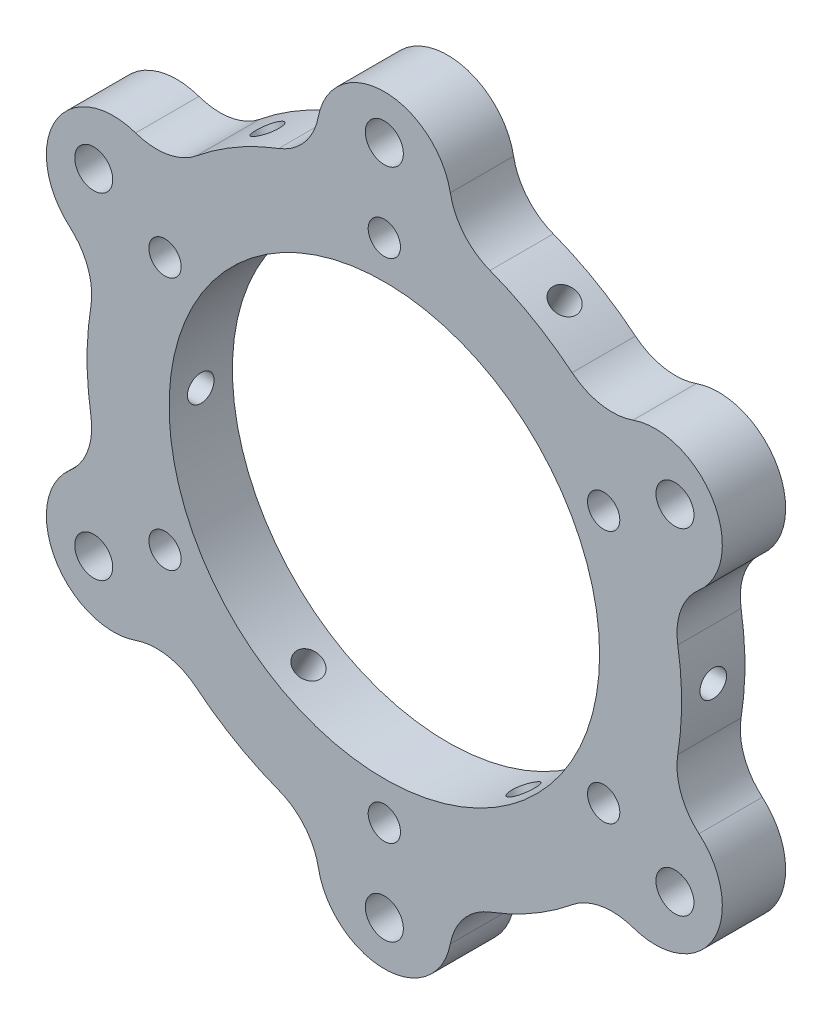
SolidWorks part; units mm, degrees
material "6063-T6"
ref_plane "Front Plane" through (0, 0, 0) normal (0, 0, 1) x (1, 0, 0)
ref_plane "Top Plane" through (0, 0, 0) normal (0, 1, 0) x (1, 0, 0)
ref_plane "Right Plane" through (0, 0, 0) normal (1, 0, 0) x (0, 0, -1)
sketch "Sketch5" plane through (0, 0, 0) normal (0, 1, 0) x (1, 0, 0)
  line L0 (0, -16.5008) -> (0, 15.0181) construction
ref_plane "Plane1" through (0, 0, 0) normal (-0.5, 0.866, 0) x (0, 0, -1)
sketch "Sketch2" plane through (0, 0, 0) normal (0, 0, 1) x (1, 0, 0)
  line L0 (0, 0) -> (0, 53) construction
  line L1 (0, 0) -> (0, 40) construction
  line L2 (0, 0) -> (0, 53) construction
  circle A0 centre (0, 0) radius 34
  circle A1 centre (0, 0) radius 60
  circle A2 centre (0, 53) radius 3
  circle A3 centre (45.8993, 26.5) radius 3
  circle A4 centre (45.8993, -26.5) radius 3
  circle A5 centre (0, -53) radius 3
  circle A6 centre (-45.8993, -26.5) radius 3
  circle A7 centre (-45.8993, 26.5) radius 3
  circle A11 centre (0, 0) radius 53 construction
  circle A12 centre (0, 40) radius 2.55
  circle A13 centre (34.641, 20) radius 2.55
  circle A14 centre (34.641, -20) radius 2.55
  circle A15 centre (0, -40) radius 2.55
  circle A16 centre (-34.641, -20) radius 2.55
  circle A17 centre (-34.641, 20) radius 2.55
  circle A18 centre (0, 0) radius 44.45 construction
  arc A19 (-16.6885, 43.8839) -> (16.6885, 43.8839) centre (0, 0) ccw
  arc A21 (-10.4177, 51.3701) -> (10.4177, 51.3701) centre (0, 49.3971) cw
  arc A22 (10.4177, 51.3701) -> (16.6885, 43.8839) centre (20.2431, 53.2308) ccw
  circle A23 centre (0, 0) radius 46.95 construction
  arc A24 (-10.4177, 51.3701) -> (-16.6885, 43.8839) centre (-20.2431, 53.2308) cw
  arc A25 (39.2789, 34.707) -> (49.6966, 16.663) centre (42.7791, 24.6985) cw
  arc A26 (39.2789, 34.707) -> (29.6603, 36.3946) centre (35.9777, 44.1464) cw
  arc A27 (49.6966, 16.663) -> (46.3488, 7.4892) centre (56.2208, 9.0844) ccw
  arc A28 (49.6966, -16.663) -> (39.2789, -34.707) centre (42.7791, -24.6985) cw
  arc A29 (49.6966, -16.663) -> (46.3488, -7.4892) centre (56.2208, -9.0844) cw
  arc A30 (39.2789, -34.707) -> (29.6603, -36.3946) centre (35.9777, -44.1464) ccw
  arc A31 (10.4177, -51.3701) -> (-10.4177, -51.3701) centre (0, -49.3971) cw
  arc A32 (10.4177, -51.3701) -> (16.6885, -43.8839) centre (20.2431, -53.2308) cw
  arc A33 (-10.4177, -51.3701) -> (-16.6885, -43.8839) centre (-20.2431, -53.2308) ccw
  arc A34 (-39.2789, -34.707) -> (-49.6966, -16.663) centre (-42.7791, -24.6985) cw
  arc A35 (-39.2789, -34.707) -> (-29.6603, -36.3946) centre (-35.9777, -44.1464) cw
  arc A36 (-49.6966, -16.663) -> (-46.3488, -7.4892) centre (-56.2208, -9.0844) ccw
  arc A37 (-49.6966, 16.663) -> (-39.2789, 34.707) centre (-42.7791, 24.6985) cw
  arc A38 (-49.6966, 16.663) -> (-46.3488, 7.4892) centre (-56.2208, 9.0844) cw
  arc A39 (-39.2789, 34.707) -> (-29.6603, 36.3946) centre (-35.9777, 44.1464) ccw
  point P24 (0, 0)
  point P42 (46.95, 0)
  point P43 (0, 0)
  point P46 (10, 45.8727)
  point P49 (-10, 45.8727)
  point P84 (0, 0)
  dimension "D1" = 6
  dimension "D2" = 68
  dimension "D3" = 120
  dimension "D6" = 6
  dimension "D7" = 88.9
  dimension "D9" = 5.1
  dimension "D4" = 0
  dimension "D11" = 20
  dimension "D12" = 10
  dimension "D5" = 6
  dimension "D8" = 2.5
  dimension "D10" = 40
  dimension "D13" = 6
extrude "Boss-Extrude1" add sketch "Sketch2" along normal blind 10 contours A21 A24 A19 A22 A0 A2 A12 A13 A14 A15 A16 A17 | A39 A37 A38 A19 A7 | A27 A25 A26 A19 A3 | A33 A31 A32 A19 A5 | A36 A34 A35 A19 A6 | A30 A28 A29 A19 A4 region at (52.8637, 22.986, 0) region at (46.3383, -34.2883, 0) region at (5.856, 56.4663, 0) region at (-6.5275, -57.2769, 0) region at (-46.3383, 34.2883, 0) region at (-52.8637, -22.986, 0)
sketch "Sketch4" plane through (0, 0, 0) normal (-0.5, 0.866, 0) x (0, 0, -1)
  line L0 (0, 0) -> (-10, 0) construction
  line L3 (-16.5008, 0) -> (15.0181, 0) construction
  line L7 (0, -7.4892) -> (0, 7.4892)
  line L8 (0, 7.4892) -> (-10, 7.4892)
  line L9 (-10, 7.4892) -> (-10, -7.4892)
  line L10 (-10, -7.4892) -> (0, -7.4892)
  line L11 (0, -7.4892) -> (0, 7.4892)
  line L12 (0, 7.4892) -> (-10, 7.4892)
  line L13 (-10, 7.4892) -> (-10, -7.4892)
  line L14 (-10, -7.4892) -> (0, -7.4892)
  circle A4 centre (-5, 0) radius 2.1
  dimension "D1" = 0
  dimension "D2" = 4.2
extrude "Cut-Extrude1" cut sketch "Sketch4" against normal through all both and the other way through all contours L0 A4 | A4 L0 region at (0.7719, 0.4456, 5) region at (-0.7719, -0.4456, 5)
pattern_circular "CirPattern1" count 6 over 360 about axis through (0, 0, 16.5008) along (0, 0, -1) of "Cut-Extrude1" reverse direction yes
